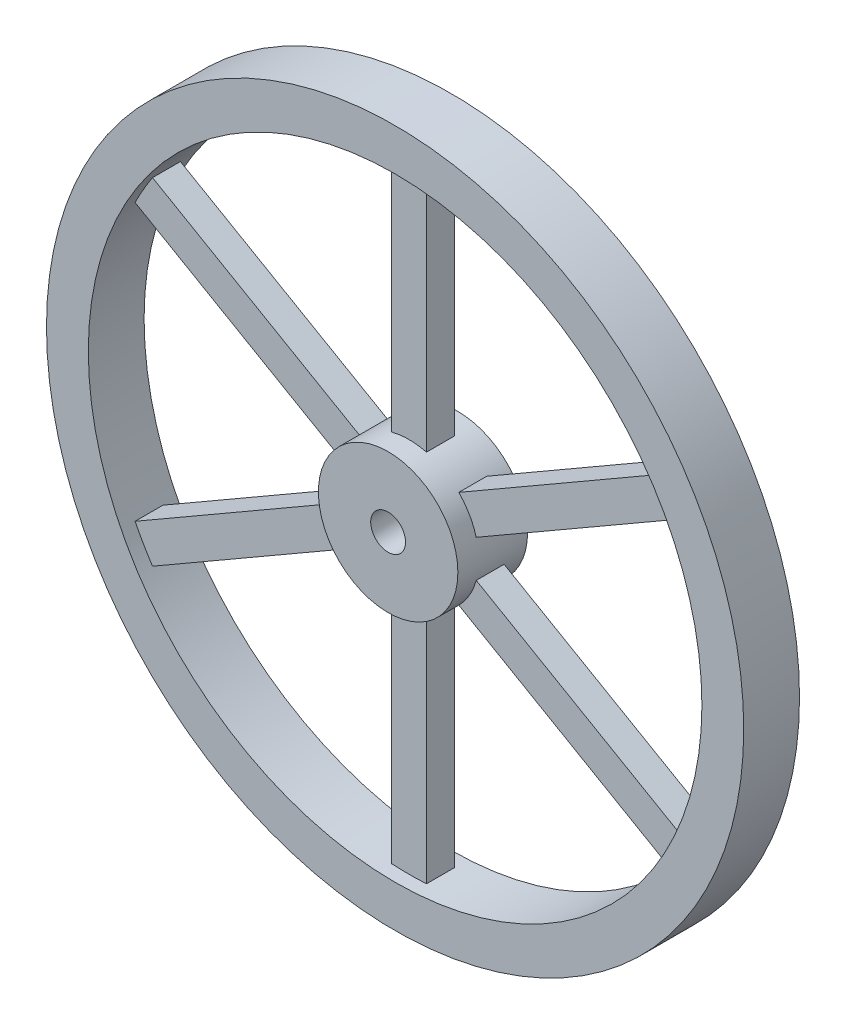
SolidWorks part; units mm, degrees
material "Gray Cast Iron"
ref_plane "Front Plane" through (0, 0, 0) normal (0, 0, 1) x (1, 0, 0)
ref_plane "Top Plane" through (0, 0, 0) normal (0, 1, 0) x (1, 0, 0)
ref_plane "Right Plane" through (0, 0, 0) normal (1, 0, 0) x (0, 0, -1)
sketch "Sketch1" plane through (0, 0, 0) normal (0, 0, 1) x (1, 0, 0)
  circle A0 centre (0, 0) radius 50
  circle A1 centre (0, 0) radius 44
  dimension "D1" = 100
  dimension "D2" = 88
extrude "Boss-Extrude1" add sketch "Sketch1" along normal mid plane 8
sketch "Sketch2" plane through (0, 0, 0) normal (0, 0, 1) x (1, 0, 0)
  circle A0 centre (0, 0) radius 10
  dimension "D1" = 20
extrude "Boss-Extrude2" add sketch "Sketch2" along normal mid plane 10
sketch "Sketch3" plane through (0, 0, 0) normal (0, 0, 1) x (1, 0, 0)
  line L0 (-2.5, 9) -> (2.5, 9)
  line L1 (2.5, 9) -> (2.5, 45)
  line L2 (2.5, 45) -> (-2.5, 45)
  line L3 (-2.5, 45) -> (-2.5, 9)
  dimension "D1" = 5
  dimension "D2" = 36
  dimension "D3" = 2.5
  dimension "D4" = 9
extrude "Boss-Extrude3" add sketch "Sketch3" along normal mid plane 4
sketch "Sketch4" plane through (0, 0, 0) normal (0, 0, 1) x (1, 0, 0)
  circle A0 centre (0, 0) radius 2.5
  dimension "D1" = 5
extrude "Cut-Extrude1" cut sketch "Sketch4" against normal mid plane 12
pattern_circular "CirPattern1" count 6 over 360 about axis through (0, 0, 5) along (0, 0, 1) of "Boss-Extrude3"
